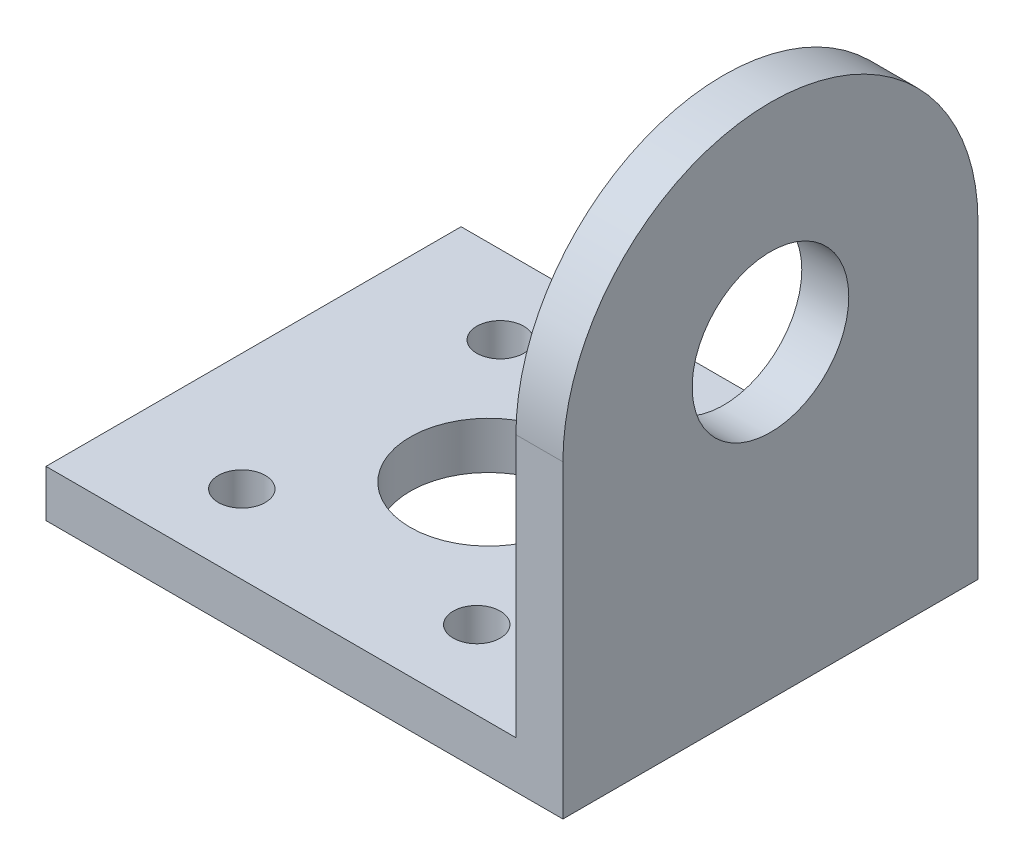
SolidWorks part; units mm, degrees
ref_plane "Front Plane" through (0, 0, 0) normal (0, 0, 1) x (1, 0, 0)
ref_plane "Top Plane" through (0, 0, 0) normal (0, 1, 0) x (1, 0, 0)
ref_plane "Right Plane" through (0, 0, 0) normal (1, 0, 0) x (0, 0, -1)
sketch "Sketch1" plane through (0, 0, 0) normal (0, 1, 0) x (1, 0, 0)
  line L0 (0, -14.5443) -> (0, 21.3613) construction
  line L1 (-15, 13.25) -> (15, 13.25)
  line L2 (-15, 13.25) -> (-15, -13.25)
  line L3 (-15, -13.25) -> (15, -13.25)
  line L4 (15, 13.25) -> (15, -13.25)
  line L5 (-15, 13.25) -> (15, -13.25) construction
  line L6 (-15, -13.25) -> (15, 13.25) construction
  line L7 (-19.6503, 0) -> (29.797, 0) construction
  circle A0 centre (0, 0) radius 5
  circle A1 centre (7.5, 8.25) radius 1.5
  circle A5 centre (-7.5, 8.25) radius 1.5
  circle A6 centre (-7.5, -8.25) radius 1.5
  circle A7 centre (7.5, -8.25) radius 1.5
  point P0 (0, 0)
  dimension "D1" = 10
  dimension "D4" = 7.5
  dimension "D6" = 3
  dimension "D5" = 5
  dimension "D2" = 26.5
  dimension "D3" = 30
extrude "Boss-Extrude1" add sketch "Sketch1" along normal blind 3
sketch "Sketch2" plane through (0, 0, 0) normal (0, 1, 0) x (1, 0, 0)
  line L0 (-15, -13.25) -> (15, -13.25) construction
  line L1 (15, 13.25) -> (18, 13.25)
  line L2 (15, 13.25) -> (15, -13.25)
  line L3 (15, -13.25) -> (18, -13.25)
  line L4 (18, 13.25) -> (18, -13.25)
  dimension "D1" = 3
  dimension "D2" = 0
extrude "Boss-Extrude2" add sketch "Sketch2" along normal blind 33
sketch "Sketch3" plane through (15, 0, 0) normal (-1, 0, 0) x (0, 0, 1)
  line L0 (-13.25, 33) -> (13.25, 33) construction
  line L2 (-13.25, 33) -> (-13.25, 19.75)
  line L4 (-13.25, 33) -> (13.25, 33)
  line L5 (13.25, 33) -> (13.25, 19.75)
  arc A0 (13.25, 19.75) -> (-13.25, 19.75) centre (0, 19.75) ccw
  line M2 (13.25, 3) -> (13.25, 33)
  line M3 (13.25, 33) -> (-13.25, 33)
  line M4 (-13.25, 33) -> (-13.25, 3)
  dimension "D1" = 26.5
extrude "Cut-Extrude1" cut sketch "Sketch3" against normal blind 33 contours A0 L4 M4 | A0 M2 M3 region at (15, 30.0404, -10.2904) region at (15, 30.0404, 10.2904)
sketch "Sketch4" plane through (18, 0, 0) normal (1, 0, 0) x (0, 0, -1)
  circle A0 centre (0, 19.75) radius 5
  dimension "D1" = 10
extrude "Cut-Extrude2" cut sketch "Sketch4" against normal through all
